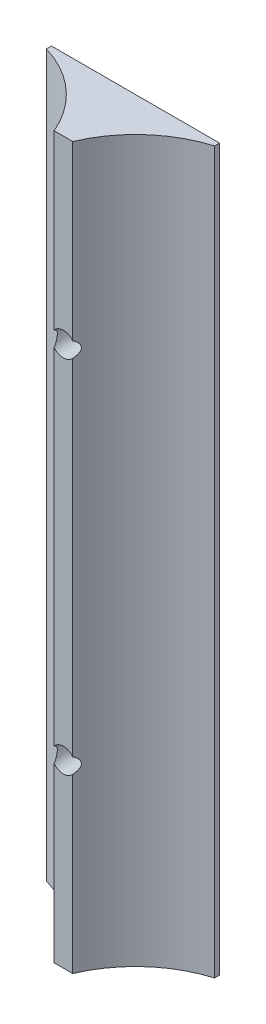
SolidWorks part; units mm, degrees
ref_plane "Front" through (0, 0, 0) normal (0, 0, 1) x (1, 0, 0)
ref_plane "Top" through (0, 0, 0) normal (0, 1, 0) x (1, 0, 0)
ref_plane "Right" through (0, 0, 0) normal (1, 0, 0) x (0, 0, -1)
sketch "Sketch1" plane through (0, 0, 0) normal (0, 1, 0) x (1, 0, 0)
  line L0 (-0.7751, 0) -> (0.7751, 0)
  line L1 (7, 5.5851) -> (7, 6)
  line L2 (7, 6) -> (-7, 6)
  line L3 (-7, 6) -> (-7, 5.5851)
  arc A0 (0.7751, 0) -> (7, 5.5851) centre (9.825, -3.825) cw
  arc A1 (-7, 5.5851) -> (-0.7751, 0) centre (-9.825, -3.825) cw
  point P9 (0, 6)
  point P10 (0, 0)
  dimension "D1" = 9.825
  dimension "D6" = 6
  dimension "D2" = 19.65
  dimension "D3" = 9.825
  dimension "D4" = 14
extrude "Boss-Extrude1" add sketch "Sketch1" along normal blind 60
sketch "Sketch3" plane through (0, 0, -6) normal (0, 0, -1) x (-1, 0, 0)
  line L0 (0, 0) -> (0, 60) construction
  line L1 (-7, 0) -> (7, 0) construction
  line L2 (-7, 60) -> (7, 60) construction
  point P6 (0, 45)
  point P7 (0, 15)
  dimension "D1" = 15
  dimension "D2" = 15
hole_wizard "Tapped Hole for M2.5x0.45 Helicoil1" positions "3DSketch1" profile "Sketch4" tap size "M2.5x0.45" standard "Helicoil® Metric"
sketch3d "3DSketch1"
  point P0 (0, 45, -6)
  point P3 (0, 15, -6)
cosmetic thread "Hole Thread1" parameters "D1"=3, "D2"=3.145
cosmetic thread "Hole Thread2" parameters "D1"=3, "D2"=3.145
sketch "Sketch4" plane through (0, 45, -6) normal (1, 0, 0) x (0, 1, 0)
  line L0 (0, 0) -> (0, 4.7661)
  line L1 (0, 4.7661) -> (1.275, 4)
  line L2 (1.275, 4) -> (1.275, 0)
  line L5 (1.275, 0) -> (0, 0)
  line L10 (0, 4.7661) -> (-1.275, 4) construction
  line L11 (0, -6.35) -> (0, 107.95) construction
  dimension "Tap Drill Dia." = 2.55
  dimension "Tap Drill Depth" = 4
  dimension "Drill Angle" = 118
hole_wizard "Ø2.0mm Dowel Hole1" positions "3DSketch2" profile "Sketch5" hole size "Ø2.0" standard "ANSI Metric"
sketch3d "3DSketch2"
  point P0 (0, 45, -6)
  point P3 (0, 15, -6)
sketch "Sketch5" plane through (0, 45, -6) normal (1, 0, 0) x (0, 1, 0)
  line L0 (0, 0) -> (0, 7.0509)
  line L1 (0, 7.0509) -> (1, 6.45)
  line L2 (1, 6.45) -> (1, 0)
  line L5 (1, 0) -> (0, 0)
  line L10 (0, 7.0509) -> (-1, 6.45) construction
  line L11 (0, -6.35) -> (0, 107.95) construction
  dimension "Hole Dia." = 2
  dimension "Hole Depth" = 6.45
  dimension "Drill Angle" = 118
